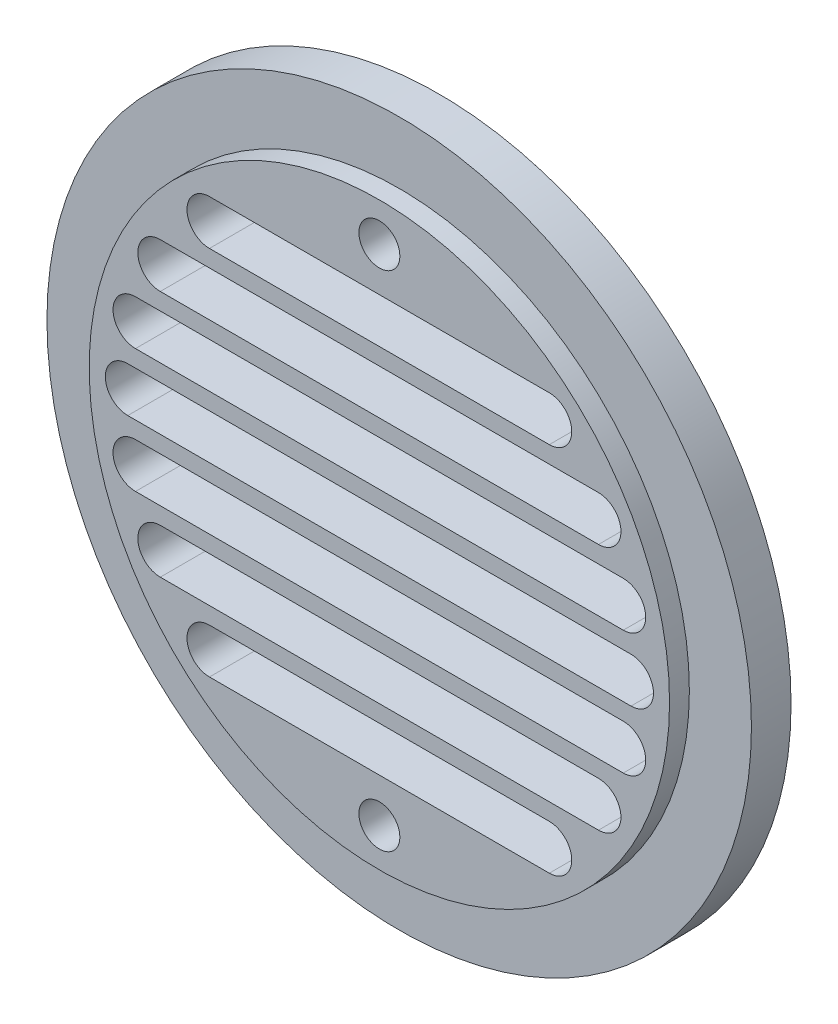
SolidWorks part; units mm, degrees
ref_plane "Front Plane" through (0, 0, 0) normal (0, 0, 1) x (1, 0, 0)
ref_plane "Top Plane" through (0, 0, 0) normal (0, 1, 0) x (1, 0, 0)
ref_plane "Right Plane" through (0, 0, 0) normal (1, 0, 0) x (0, 0, -1)
sketch "Sketch1" plane through (0, 0, 0) normal (0, 0, 1) x (1, 0, 0)
  circle A0 centre (0, 0) radius 26.67
  circle A1 centre (0, 0) radius 21.971
  circle A2 centre (0, 0) radius 18.5
  dimension "D1" = 43.942
  dimension "D2" = 53.34
  dimension "D3" = 37
extrude "Boss-Extrude1" add sketch "Sketch1" along normal blind 3 contours A0 A1 | A1 A2 | A2 region at (-25.9157, 0, 0) region at (-21.3496, 0, 0) region at (0, 0, 0)
extrude "Boss-Extrude2" add sketch "Sketch1<3>" along normal offset from surface (4.5 mm away) 1.5 contours A1 A2 | A2 region at (-21.3496, 0, 0) region at (0, 0, 0) up to face at (26.67, 0, 3) offset beyond the face yes
sketch "Sketch1<3>" plane through (0, 0, 0) normal (0, 0, 1) x (1, 0, 0) same geometry as "Sketch1"
sketch "Sketch2" plane through (0, 0, 4.5) normal (0, 0, 1) x (1, 0, 0)
  line L0 (-12.8647, 14.05) -> (12.8647, 14.05) construction
  line L1 (-16.5882, 9.3667) -> (16.5882, 9.3667) construction
  line L2 (-18.4653, 4.6833) -> (18.4653, 4.6833) construction
  line L3 (-18.4653, -4.6833) -> (18.4653, -4.6833) construction
  line L4 (-16.5882, -9.3667) -> (16.5882, -9.3667) construction
  line L5 (-12.8647, -14.05) -> (12.8647, -14.05) construction
  line L6 (0, -14.05) -> (0, -9.3667) construction
  line L7 (0, -9.3667) -> (0, -4.6833) construction
  line L8 (-19.05, 0) -> (19.05, 0) construction
  line L9 (0, 4.6833) -> (0, 9.3667) construction
  line L10 (0, 9.3667) -> (0, 14.05) construction
  line L11 (0, 0) -> (0, 4.6833) construction
  line L12 (0, 0) -> (0, -4.6833) construction
  line L13 (-12.8647, 12.35) -> (12.8647, 12.35)
  line L14 (-16.5882, 7.6667) -> (16.5882, 7.6667)
  line L15 (-18.4653, 2.9833) -> (18.4653, 2.9833)
  line L16 (-19.05, -1.7) -> (19.05, -1.7)
  line L17 (-18.4653, -6.3833) -> (18.4653, -6.3833)
  line L18 (-16.5882, -11.0667) -> (16.5882, -11.0667)
  line L19 (-12.8647, -15.75) -> (12.8647, -15.75)
  line L20 (-12.8647, 15.75) -> (12.8647, 15.75)
  line L21 (-16.5882, 11.0667) -> (16.5882, 11.0667)
  line L22 (-18.4653, 6.3833) -> (18.4653, 6.3833)
  line L23 (-19.05, 1.7) -> (19.05, 1.7)
  line L24 (-18.4653, -2.9833) -> (18.4653, -2.9833)
  line L25 (-16.5882, -7.6667) -> (16.5882, -7.6667)
  line L26 (-12.8647, -12.35) -> (12.8647, -12.35)
  circle A0 centre (0, 0) radius 19.05 construction
  circle A1 centre (0, 19.05) radius 1.55
  circle A2 centre (0, -19.05) radius 1.55
  arc A3 (-12.8647, 12.35) -> (-12.8647, 15.75) centre (-12.8647, 14.05) cw
  arc A4 (12.8647, 12.35) -> (12.8647, 15.75) centre (12.8647, 14.05) ccw
  arc A5 (-16.5882, 7.6667) -> (-16.5882, 11.0667) centre (-16.5882, 9.3667) cw
  arc A6 (16.5882, 7.6667) -> (16.5882, 11.0667) centre (16.5882, 9.3667) ccw
  arc A7 (-18.4653, 2.9833) -> (-18.4653, 6.3833) centre (-18.4653, 4.6833) cw
  arc A8 (18.4653, 2.9833) -> (18.4653, 6.3833) centre (18.4653, 4.6833) ccw
  arc A9 (-19.05, -1.7) -> (-19.05, 1.7) centre (-19.05, 0) cw
  arc A10 (19.05, -1.7) -> (19.05, 1.7) centre (19.05, 0) ccw
  arc A11 (-18.4653, -6.3833) -> (-18.4653, -2.9833) centre (-18.4653, -4.6833) cw
  arc A12 (18.4653, -6.3833) -> (18.4653, -2.9833) centre (18.4653, -4.6833) ccw
  arc A13 (-16.5882, -11.0667) -> (-16.5882, -7.6667) centre (-16.5882, -9.3667) cw
  arc A14 (16.5882, -11.0667) -> (16.5882, -7.6667) centre (16.5882, -9.3667) ccw
  arc A15 (-12.8647, -15.75) -> (-12.8647, -12.35) centre (-12.8647, -14.05) cw
  arc A16 (12.8647, -15.75) -> (12.8647, -12.35) centre (12.8647, -14.05) ccw
  dimension "D1" = 38.1
  dimension "D2" = 3.1
  dimension "D3" = 5
  dimension "D4" = 5
extrude "Cut-Extrude2" cut sketch "Sketch2" against normal through all
